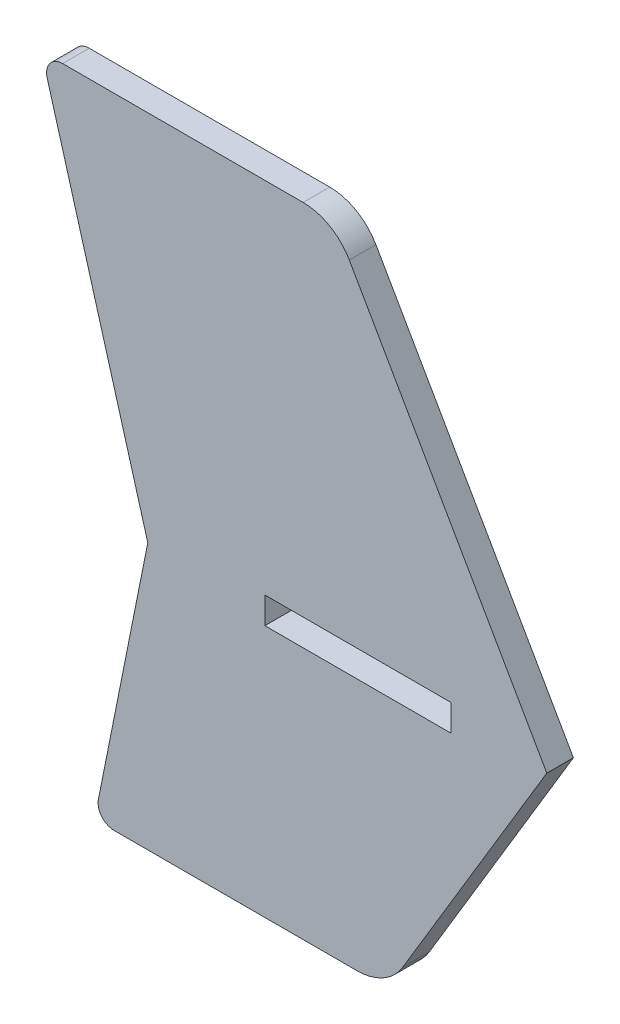
SolidWorks part; units mm, degrees
ref_plane "Ebene vorne" through (0, 0, 0) normal (0, 0, 1) x (1, 0, 0)
ref_plane "Ebene oben" through (0, 0, 0) normal (0, 1, 0) x (1, 0, 0)
ref_plane "Ebene rechts" through (0, 0, 0) normal (1, 0, 0) x (0, 0, -1)
sketch "Skizze1" plane through (0, 0, 0) normal (0, 0, 1) x (1, 0, 0)
  line L1 (-35, 120) -> (20, 120)
  line L2 (20, 120) -> (60, 50)
  line L3 (60, 50) -> (30, 0)
  line L4 (30, 0) -> (0, 0)
  line L5 (-35, 120) -> (-15, 50)
  line L6 (-15, 50) -> (-25, 0)
  line L7 (-25, 0) -> (0, 0)
  point P3 (0, 0)
  dimension "D1" = 120
  dimension "D2" = 55
  dimension "D3" = 30
  dimension "D4" = 40
  dimension "D5" = 50
  dimension "D6" = 30
  dimension "D7" = 25
  dimension "D8" = 75
extrude "Grundplatte" add sketch "Skizze1" along normal blind 5 contours L1 L2 L3 L4 L7 L6 L5
sketch "Skizze2" plane through (0, 0, 5) normal (0, 0, 1) x (1, 0, 0)
  line L1 (7, 47.5) -> (42, 47.5)
  line L2 (7, 47.5) -> (7, 52.5)
  line L3 (7, 52.5) -> (42, 52.5)
  line L4 (42, 47.5) -> (42, 52.5)
  line L5 (42, 50) -> (60, 50) construction
  dimension "D1" = 35
  dimension "D2" = 5
  dimension "D3" = 18
extrude "NutHöhenleitwerk" cut sketch "Skizze2" against normal blind 15
fillet "Verrundung1" radius 10 2 edges at (30, 0, 2.5) (20, 120, 2.5)
fillet "Verrundung2" radius 3 2 edges at (-25, 0, 2.5) (-35, 120, 2.5)
